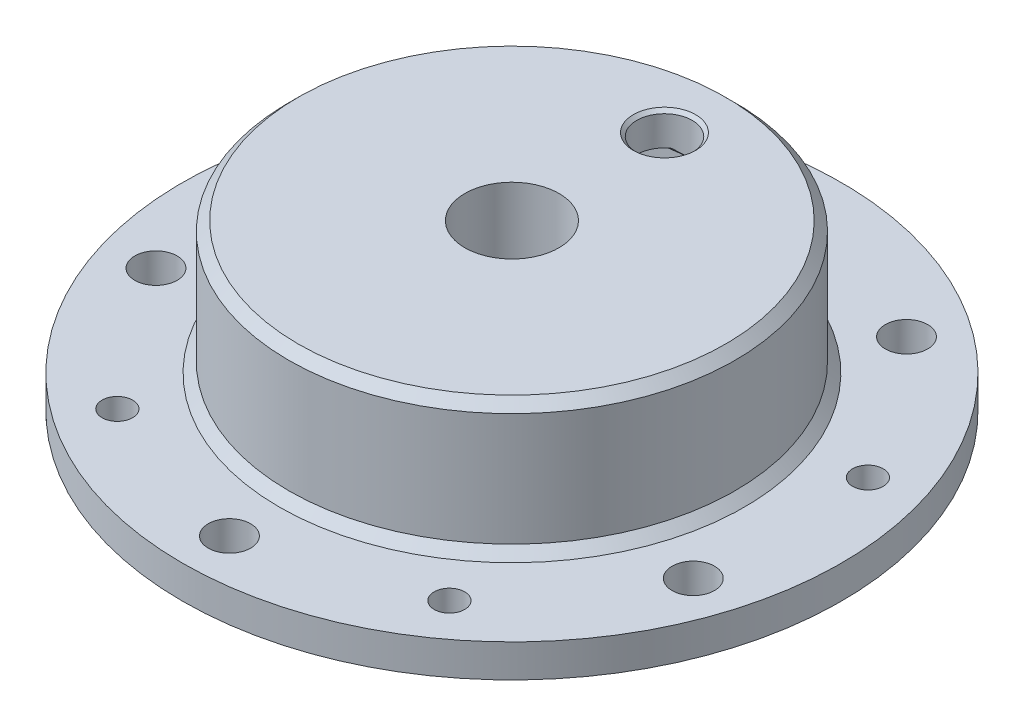
SolidWorks part; units mm, degrees
material "1023 Carbon Steel Sheet (SS)"
ref_plane "Front Plane" through (0, 0, 0) normal (0, 0, 1) x (1, 0, 0)
ref_plane "Top Plane" through (0, 0, 0) normal (0, 1, 0) x (1, 0, 0)
ref_plane "Right Plane" through (0, 0, 0) normal (1, 0, 0) x (0, 0, -1)
sketch "Sketch1" plane through (0, 0, 0) normal (0, 0, 1) x (1, 0, 0)
  line L0 (0, 0) -> (-10, 0) construction
  line L1 (-10, 0) -> (-10, -35)
  line L2 (-10, -35) -> (-12.5, -35)
  line L3 (-12.5, -35) -> (-12.5, -33.2)
  line L4 (-12.7, -33) -> (-15.542, -33)
  line L5 (-15.75, -33.208) -> (-15.75, -35)
  line L6 (-15.75, -35) -> (-18.5, -35)
  line L7 (-18.5, -35) -> (-18.5, -33.208)
  line L8 (-18.708, -33) -> (-21.542, -33)
  line L9 (-21.75, -33.208) -> (-21.75, -35)
  line L10 (-21.75, -35) -> (-24, -35)
  line L11 (-24, -35) -> (-24, -7)
  line L13 (-39.4, -7) -> (-39.4, -35)
  line L14 (-39.4, -35) -> (-42, -35)
  line L15 (-42, -35) -> (-42, -33.208)
  line L16 (-42.208, -33) -> (-45.042, -33)
  line L17 (-45.25, -33.208) -> (-45.25, -35)
  line L18 (-45.25, -35) -> (-47.75, -35)
  line L19 (-47.75, -35) -> (-47.75, -33.208)
  line L20 (-47.958, -33) -> (-50.792, -33)
  line L21 (-51, -33.208) -> (-51, -35)
  line L22 (-51, -35) -> (-70, -35)
  line L23 (-70, -35) -> (-70, -28)
  line L24 (-70, -28) -> (-47.4, -28)
  line L25 (-47.4, -28) -> (-47.4, 0)
  line L26 (-47.4, 0) -> (-10, 0)
  line L28 (-39.4, -7) -> (-24, -7)
  line L29 (0, 0) -> (0, -83.2336) construction
  arc A0 (-12.5, -33.2) -> (-12.7, -33) centre (-12.7, -33.2) ccw
  arc A1 (-15.542, -33) -> (-15.75, -33.208) centre (-15.542, -33.208) ccw
  arc A2 (-21.542, -33) -> (-21.75, -33.208) centre (-21.542, -33.208) ccw
  arc A3 (-18.5, -33.208) -> (-18.708, -33) centre (-18.708, -33.208) ccw
  arc A4 (-50.792, -33) -> (-51, -33.208) centre (-50.792, -33.208) ccw
  arc A5 (-47.75, -33.208) -> (-47.958, -33) centre (-47.958, -33.208) ccw
  arc A6 (-45.042, -33) -> (-45.25, -33.208) centre (-45.042, -33.208) ccw
  arc A7 (-42, -33.208) -> (-42.208, -33) centre (-42.208, -33.208) ccw
  point P30 (-12.5, -33)
  point P33 (-15.75, -33)
  point P36 (-21.75, -33)
  point P39 (-18.5, -33)
  point P42 (-51, -33)
  point P45 (-47.75, -33)
  point P48 (-45.25, -33)
  point P51 (-42, -33)
  dimension "D26" = 0.2
  dimension "D27" = 0.208
  dimension "D28" = 0.208
  dimension "D29" = 0.208
  dimension "D1" = 10
  dimension "D2" = 35
  dimension "D3" = 2.5
  dimension "D4" = 2
  dimension "D5" = 3.25
  dimension "D6" = 2
  dimension "D7" = 2.75
  dimension "D8" = 2
  dimension "D9" = 3.25
  dimension "D10" = 2
  dimension "D11" = 2.25
  dimension "D12" = 28
  dimension "D13" = 15.4
  dimension "D14" = 28
  dimension "D15" = 28
  dimension "D16" = 22.6
  dimension "D17" = 7
  dimension "D18" = 2.6
  dimension "D19" = 2
  dimension "D20" = 3.25
  dimension "D21" = 2.5
  dimension "D22" = 2
  dimension "D23" = 2
  dimension "D24" = 3.25
  dimension "D25" = 37.4
revolve "Revolve1" add sketch "Sketch1" angle 360 about L29
sketch "Sketch2" plane through (0, 0, 0) normal (0, 1, 0) x (1, 0, 0)
  point P0 (0, 32.4)
  dimension "D1" = 32.4
hole_wizard "G1/4 Tapped Hole1" positions "Sketch3" profile "Sketch4" tap size "G1/4" standard "BSI" end condition up to next
sketch "Sketch3" plane through (0, 0, 0) normal (0, 1, 0) x (1, 0, 0)
  point P0 (0, 32.4)
sketch "Sketch4" plane through (0, 0, -32.4) normal (1, 0, 0) x (0, 0, 1)
  line L0 (0, 0) -> (0, 7)
  line L1 (0, 7) -> (5.9, 7)
  line L2 (5.9, 7) -> (5.9, 0.7035)
  line L3 (5.9, 0.7035) -> (6.6035, 0)
  line L5 (6.6035, 0) -> (0, 0)
  line L6 (-5.9, 0.7035) -> (-6.6035, 0) construction
  line L11 (0, -6.35) -> (0, 107.95) construction
  dimension "Thru Tap Drill Dia." = 11.8
  dimension "Thru Tap Drill Depth" = 7
  dimension "Near C'Sink Dia." = 13.207
  dimension "Near C'Sink Angle" = 90
cosmetic thread "Hole Thread1" parameters "D2"=13.157
sketch "Sketch5" plane through (0, -28, 0) normal (0, 1, 0) x (1, 0, 0)
  line L0 (0, 70) -> (0, 0) construction
  line L1 (0, 0) -> (-41.145, 56.6312) construction
  circle A0 centre (0, 60) radius 3.25
  circle A1 centre (0, 0) radius 70 construction
  circle A2 centre (-35.2671, 48.541) radius 4.5
  point P0 (0, 60)
  point P10 (0, 0)
  point P11 (0, 0)
  dimension "D2" = 6.5
  dimension "D3" = 9
  dimension "D1" = 60
  dimension "D4" = 60
  dimension "D5" = 36
extrude "Cut-Extrude1" cut sketch "Sketch5" against normal blind 10
sketch "Sketch6" plane through (0, 0, 0) normal (0, 0, 1) x (1, 0, 0)
  line L0 (0, -22.7338) -> (0, 22.818) construction
pattern_circular "CirPattern1" count 5 over 360 about axis through (0, -22.7338, 0) along (0, 1, 0) of "Cut-Extrude1" reverse direction yes
chamfer "Chamfer1" distance 2 angle 45 4 edges at (0, -7, 39.4) (0, 0, 47.4) (0, -7, 24) (0, -28, 47.4)
equation "\"Bolts\"= 10"
equation "\"D5@Sketch5\"=360/\"Bolts\""
